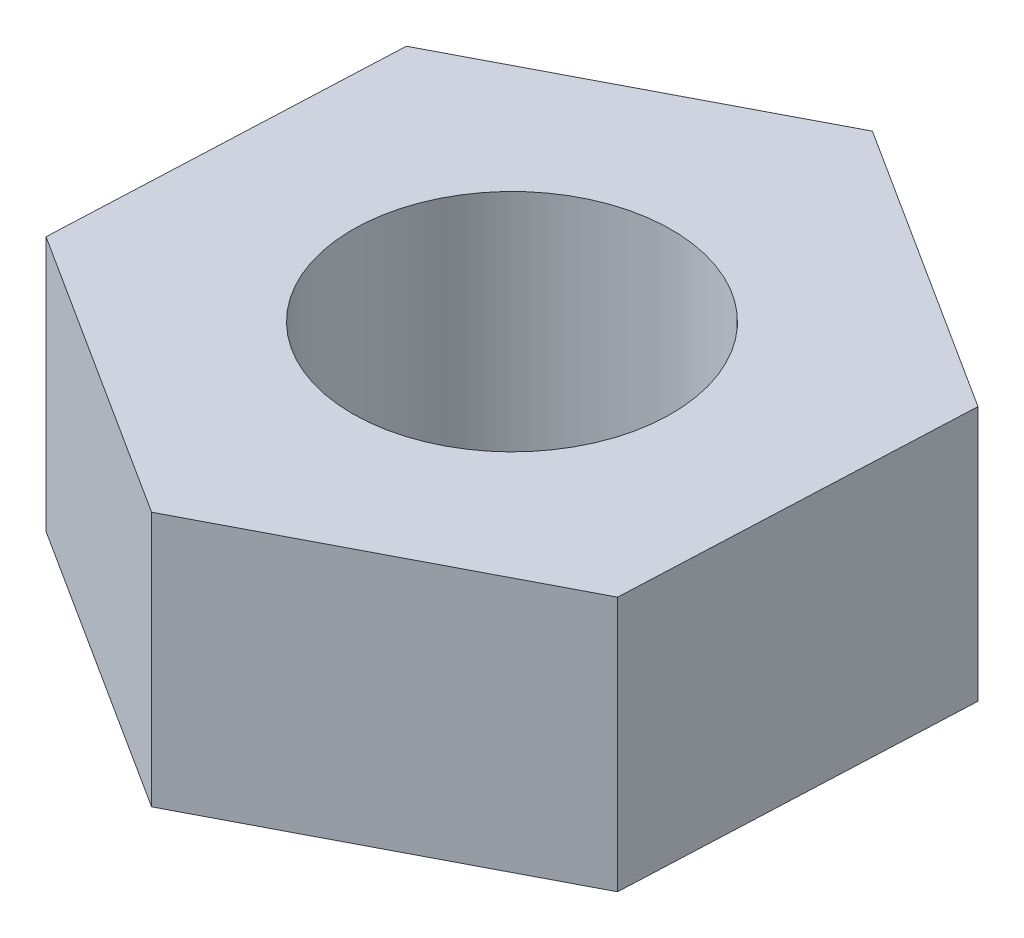
SolidWorks part; units mm, degrees
ref_plane "Front Plane" through (0, 0, 0) normal (0, 0, 1) x (1, 0, 0)
ref_plane "Top Plane" through (0, 0, 0) normal (0, 1, 0) x (1, 0, 0)
ref_plane "Right Plane" through (0, 0, 0) normal (1, 0, 0) x (0, 0, -1)
sketch "Sketch1" plane through (0, 0, 0) normal (0, 1, 0) x (1, 0, 0)
  line L1 (5.4808, -3.4944) -> (5.7666, 2.9993)
  line L2 (5.7666, 2.9993) -> (0.2858, 6.4937)
  line L3 (0.2858, 6.4937) -> (-5.4808, 3.4944)
  line L4 (-5.4808, 3.4944) -> (-5.7666, -2.9993)
  line L5 (-5.7666, -2.9993) -> (-0.2858, -6.4937)
  line L6 (-0.2858, -6.4937) -> (5.4808, -3.4944)
  circle A0 centre (0, 0) radius 5.6292 construction
extrude "Boss-Extrude1" add sketch "Sketch1" along normal blind 4.8
sketch "Sketch2" plane through (0, 4.8, 0) normal (0, 1, 0) x (1, 0, 0)
  circle A0 centre (0, 0) radius 3
extrude "Cut-Extrude1" cut sketch "Sketch2" against normal blind 5.5
move or copy body "Body-Move/Copy1" [suppressed] bodies to move or copy 102
